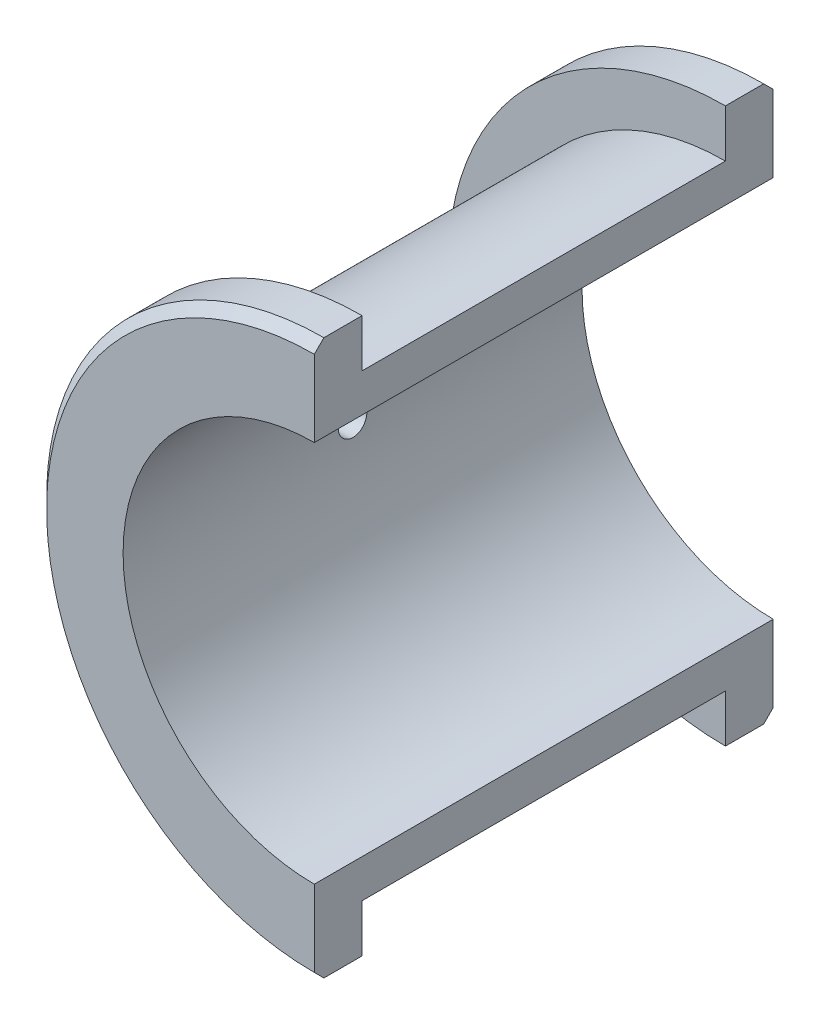
SolidWorks part; units mm, degrees
material "Бронза"
ref_plane "Спереди" through (0, 0, 0) normal (0, 0, 1) x (1, 0, 0)
ref_plane "Сверху" through (0, 0, 0) normal (0, 1, 0) x (1, 0, 0)
ref_plane "Справа" through (0, 0, 0) normal (1, 0, 0) x (0, 0, -1)
sketch "Эскиз1" plane through (0, 0, 0) normal (0, 0, 1) x (1, 0, 0)
  circle A0 centre (0, 0) radius 20
  circle A1 centre (0, 0) radius 24
  dimension "D1" = 40
  dimension "D2" = 48
extrude "Бобышка-Вытянуть1" add sketch "Эскиз1" along normal blind 24
sketch "Эскиз2" plane through (0, 0, 24) normal (0, 0, 1) x (1, 0, 0)
  circle A0 centre (0, 0) radius 29
  circle A1 centre (0, 0) radius 24
  circle A2 centre (0, 0) radius 24
  dimension "D2" = 58
  dimension "D1" = 0
extrude "Бобышка-Вытянуть2" add sketch "Эскиз2" against normal blind 5
mirror "Зеркальное отражение1" about plane through (0, 0, 0) normal (0, 0, 1) of bodies 106
sketch "Эскиз5" plane through (0, 0, 24) normal (0, 0, 1) x (1, 0, 0)
  line L1 (0, -29) -> (29, -29)
  line L2 (0, -29) -> (0, 29)
  line L3 (0, 29) -> (29, 29)
  line L4 (29, -29) -> (29, 29)
  circle A0 centre (0, 0) radius 29 construction
extrude "Вырез-Вытянуть1" cut sketch "Эскиз5" against normal through all
chamfer "Фаска2" distance 1 angle 45 2 edges at (-29, 0, -24) (-29, 0, 24)
sketch "Эскиз6" plane through (0, 0, 0) normal (1, 0, 0) x (0, 0, -1)
  circle A0 centre (0, 0) radius 4
  circle A1 centre (0, 0) radius 1.5
  dimension "D1" = 8
  dimension "D2" = 3
extrude "Бобышка-Вытянуть3" add sketch "Эскиз6" along normal up to surface (6 mm away) from offset 30 up to face at (-12, 0, 0) offset against normal yes
extrude "Вырез-Вытянуть2" cut sketch "Эскиз6<2>" against normal through all contours A1 region at (0, 0, 0)
sketch "Эскиз6<2>" plane through (0, 0, 0) normal (1, 0, 0) x (0, 0, -1) same geometry as "Эскиз6"
